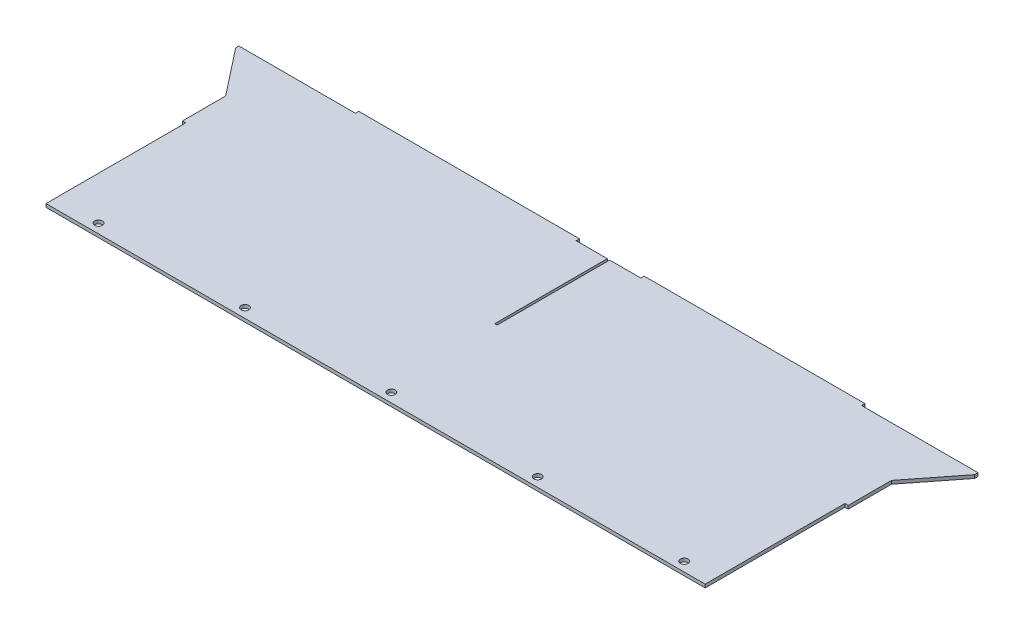
SolidWorks part; units mm, degrees
material "6061-T6 (SS)"
ref_plane "X-Y Datum" through (0, 0, 0) normal (0, 0, 1) x (1, 0, 0)
ref_plane "X-Z Datum" through (0, 0, 0) normal (0, 1, 0) x (1, 0, 0)
ref_plane "Y-Z Datum" through (0, 0, 0) normal (1, 0, 0) x (0, 0, -1)
sketch "Sketch1" plane through (0, 0, 0) normal (0, 1, 0) x (1, 0, 0)
  line L1 (-317.6778, 111.125) -> (317.6778, 111.125)
  line L2 (-317.6778, 111.125) -> (-317.6778, -111.125)
  line L3 (-317.6778, -111.125) -> (317.6778, -111.125)
  line L4 (317.6778, 111.125) -> (317.6778, -111.125)
  line L5 (-317.6778, 111.125) -> (317.6778, -111.125) construction
  line L6 (-317.6778, -111.125) -> (317.6778, 111.125) construction
  point P0 (0, 0)
  dimension "D1" = 635.3556
  dimension "D2" = 222.25
extrude "Boss-Extrude1" add sketch "Sketch1" along normal mid plane 3.175
sketch "Sketch2" plane through (0, 0, -111.125) normal (0, 0, -1) x (-1, 0, 0)
  line L0 (-241.4778, -1.5875) -> (-241.4778, 1.5875) construction
  line L1 (241.4778, -1.5875) -> (241.4778, 1.5875)
  line L2 (-241.4778, -1.5875) -> (-241.4778, 1.5875)
  line L3 (-241.4778, -1.5875) -> (-241.4778, 1.5875)
  line L4 (241.4778, -1.5875) -> (241.4778, 1.5875) construction
  line L5 (241.4778, -1.5875) -> (241.4778, 1.5875)
  line L20 (-317.6778, -1.5875) -> (317.6778, -1.5875) construction
  line L21 (-241.4778, -1.5875) -> (-30.8229, -1.5875)
  line L22 (30.8229, -1.5875) -> (241.4778, -1.5875)
  line L40 (30.8229, -1.5875) -> (30.8229, 1.5875)
  line L41 (30.8229, 1.5875) -> (241.4778, 1.5875)
  line L57 (-241.4778, 1.5875) -> (-30.8229, 1.5875)
  line L58 (-30.8229, 1.5875) -> (-30.8229, -1.5875)
  line M22 (-317.6778, -1.5875) -> (317.6778, -1.5875)
  line M24 (317.6778, 1.5875) -> (-317.6778, 1.5875)
extrude "Boss-Extrude2" add sketch "Sketch2" along normal blind 3.175 contours L58 L2 M24 M22 | L40 L1 M22 M24 region at (-136.1504, 0, -111.125) region at (136.1504, 0, -111.125)
sketch "Sketch3" plane through (0, 1.5875, 0) normal (0, 1, 0) x (1, 0, 0)
  line L0 (-317.6778, 111.125) -> (-352.6028, 111.125)
  line L1 (-352.6028, 111.125) -> (-352.6028, 107.95)
  line L2 (-352.6028, 107.95) -> (-317.6778, 63.5)
  line L3 (-317.6778, 111.125) -> (-317.6778, -111.125) construction
  line L16 (317.6778, -111.125) -> (317.6778, 111.125)
  line L17 (317.6778, 111.125) -> (241.4778, 111.125)
  line L18 (241.4778, 111.125) -> (241.4778, 114.3)
  line L19 (30.8229, 114.3) -> (30.8229, 111.125)
  line L20 (30.8229, 111.125) -> (-30.8229, 111.125)
  line L21 (-30.8229, 111.125) -> (-30.8229, 114.3)
  line L22 (-241.4778, 114.3) -> (-241.4778, 111.125)
  line L23 (-241.4778, 111.125) -> (-317.6778, 111.125)
  line L24 (241.4778, 114.3) -> (30.8229, 114.3)
  line L25 (241.4778, 114.3) -> (30.8229, 114.3)
  line L26 (-317.6778, 111.125) -> (-317.6778, -111.125)
  line L27 (-317.6778, -111.125) -> (317.6778, -111.125)
  line L38 (-317.6778, 111.125) -> (-317.6778, 63.5)
  line L40 (-30.8229, 114.3) -> (-241.4778, 114.3)
  line L41 (-30.8229, 114.3) -> (-241.4778, 114.3)
  line M26 (-317.6778, 111.125) -> (-317.6778, -111.125)
  dimension "D1" = 34.925
  dimension "D2" = 3.175
  dimension "D3" = 44.45
  dimension "D4" = 0
extrude "Boss-Extrude3" add sketch "Sketch3" against normal blind 3.175 contours L1 L2 L0 M26 region at (-330.0471, 1.5875, -95.1839)
mirror "Mirror1" about plane through (0, 0, 0) normal (1, 0, 0) of "Boss-Extrude3"
sketch "Sketch4" plane through (0, 1.5875, 0) normal (0, 1, 0) x (1, 0, 0)
  line L0 (-273.2278, -111.125) -> (-273.2278, -102.235)
  line L1 (-317.6778, -111.125) -> (317.6778, -111.125) construction
  line L2 (-273.2278, -102.235) -> (-317.6778, -102.235)
  line L3 (-317.6778, 63.5) -> (-317.6778, -111.125) construction
  circle A0 centre (-273.2278, -102.235) radius 3.675
extrude "Cut-Extrude1" cut sketch "Sketch4" against normal blind 10 contours L0 A0 L2 | L2 A0 L0 region at (-274.7875, 1.5875, 103.7947) region at (-272.7079, 1.5875, 101.7151)
pattern_linear "LPattern1" count 5 spacing 139.7 along (1, 0, 0) of "Cut-Extrude1"
sketch "Sketch6" plane through (0, 1.5875, 0) normal (0, 1, 0) x (1, 0, 0)
  line L0 (0, -191.7444) -> (0, 191.7444) construction
  line L1 (317.6778, -111.125) -> (314.5028, -111.125)
  line L2 (317.6778, -111.125) -> (317.6778, 22.225)
  line L3 (317.6778, 22.225) -> (314.5028, 22.225)
  line L4 (314.5028, -111.125) -> (314.5028, 22.225)
  line L5 (-317.6778, -111.125) -> (-314.5028, -111.125)
  line L6 (-317.6778, 22.225) -> (-314.5028, 22.225)
  line L7 (-317.6778, -111.125) -> (-317.6778, 22.225)
  line L8 (-314.5028, -111.125) -> (-314.5028, 22.225)
  line L9 (30.8229, 111.125) -> (-30.8229, 111.125) construction
  line L10 (1.143, 111.125) -> (-1.143, 111.125)
  line L11 (1.143, 111.125) -> (1.143, 3.683)
  line L12 (1.143, 3.683) -> (-1.143, 3.683)
  line L13 (-1.143, 111.125) -> (-1.143, 3.683)
  line L14 (0, 3.683) -> (0, 111.125) construction
  point P9 (0, 0)
  dimension "D1" = 3.175
  dimension "D2" = 133.35
  dimension "D3" = 107.442
  dimension "D4" = 2.286
extrude "Cut-Extrude2" cut sketch "Sketch6" against normal through all
